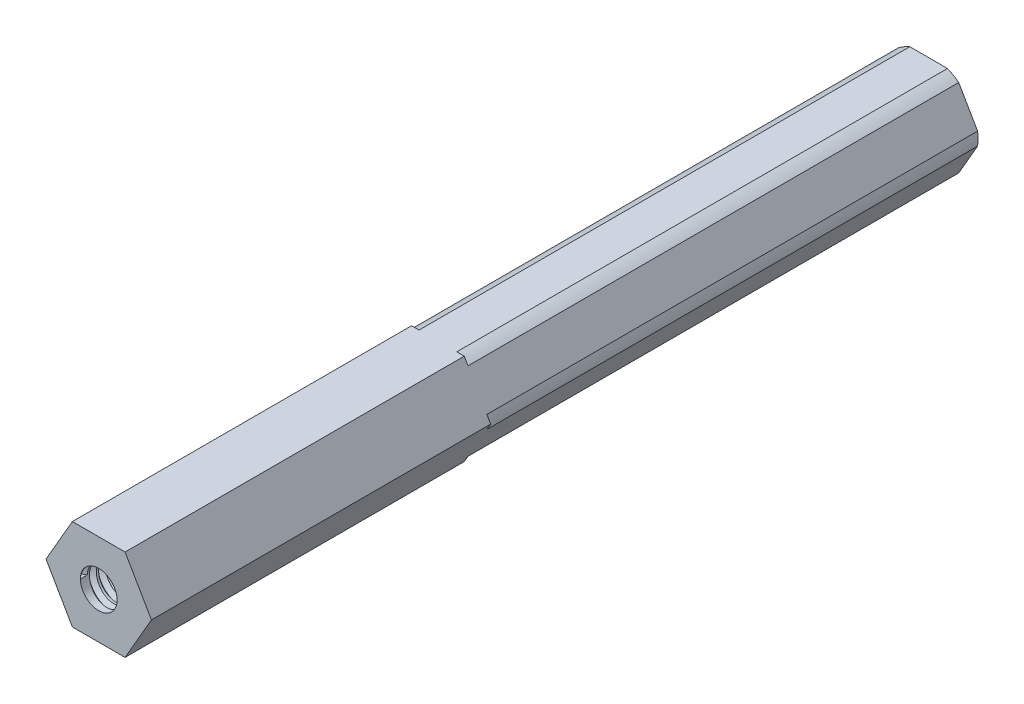
SolidWorks part; units mm, degrees
material "7075-T6 (SN)"
ref_plane "Alzado" through (0, 0, 0) normal (0, 0, 1) x (1, 0, 0)
ref_plane "Planta" through (0, 0, 0) normal (0, 1, 0) x (1, 0, 0)
ref_plane "Vista lateral" through (0, 0, 0) normal (1, 0, 0) x (0, 0, -1)
sketch "Croquis2" plane through (0, 0, 0) normal (0, 0, 1) x (1, 0, 0)
  line L1 (3.6662, -6.35) -> (7.3323, 0)
  line L2 (7.3323, 0) -> (3.6662, 6.35)
  line L3 (3.6662, 6.35) -> (-3.6662, 6.35)
  line L4 (-3.6662, 6.35) -> (-7.3323, 0)
  line L5 (-7.3323, 0) -> (-3.6662, -6.35)
  line L6 (-3.6662, -6.35) -> (3.6662, -6.35)
  circle A0 centre (0, 0) radius 6.35 construction
  dimension "D1" = 12.7
extrude "Extrusión Hex Profile" add sketch "Croquis2" along normal mid plane 115.4176
sketch "Croquis3" plane through (0, 0, 0) normal (0, 0, 1) x (1, 0, 0)
  circle A0 centre (0, 0) radius 2.5527
  dimension "D1" = 5.1054
extrude "Tap Hole 1" cut sketch "Croquis3" against normal blind 19.05 from surface starting at face at (0, 0, 57.7088)
extrude "Tap Hole 2" cut sketch "Croquis3<3>" along normal blind 19.05 from surface starting at face at (0, 0, -57.7088)
sketch "Croquis3<3>" plane through (0, 0, 0) normal (0, 0, 1) x (1, 0, 0) same geometry as "Croquis3"
sketch "Croquis7" plane through (0, 0, 0) normal (0, 0, 1) x (1, 0, 0)
  circle A0 centre (0, 0) radius 6.8707
  dimension "D1" = 13.7414
extrude "ThunderHex" cut sketch "Croquis7" along normal offset from surface (68.2498 mm away) 47.1678 from surface flip side to cut up to face at (2.5527, 0, 57.7088) starting at face at (2.5527, 0, -57.7088)
sketch "Croquis8" plane through (0, 0, 0) normal (0, 1, 0) x (1, 0, 0)
  line L0 (0, -57.7088) -> (-5.5562, -57.7088) construction
  line L1 (3.6662, -57.7088) -> (-3.6662, -57.7088) construction
  line L3 (0, -57.7088) -> (0, 0) construction
  line L4 (-5.5562, -57.7088) -> (-6.35, -56.915)
  line L5 (-6.35, -56.915) -> (-6.35, -56.1213)
  line L6 (-6.35, -56.1213) -> (-5.9055, -56.1213)
  line L7 (-5.9055, -56.1213) -> (-5.9055, -54.5338)
  line L8 (-5.9055, -54.5338) -> (-12.7, -54.5338)
  line L9 (-12.7, -54.5338) -> (-12.7, -57.7088)
  line L10 (-12.7, -57.7088) -> (-5.5562, -57.7088)
  line L11 (-3.6662, -57.7088) -> (-7.3323, -57.7088) construction
  dimension "D1" = 11.811
  dimension "D2" = 12.7
  dimension "D3" = 45
  dimension "D4" = 0.7937
  dimension "D6" = 0.7937
  dimension "D7" = 3.175
  dimension "D8" = 25.4
revolve "Retaining Ring 1" [suppressed] cut sketch "Croquis8" angle 360 about L3
sketch "Croquis9" plane through (0, 0, 0) normal (0, -1, 0) x (1, 0, 0)
  line L0 (0, -57.7088) -> (-5.5562, -57.7088) construction
  line L3 (0, -57.7088) -> (0, 0) construction
  line L4 (-5.5562, -57.7088) -> (-6.35, -56.915)
  line L5 (-6.35, -56.915) -> (-6.35, -56.1213)
  line L6 (-6.35, -56.1213) -> (-5.9055, -56.1213)
  line L7 (-5.9055, -56.1213) -> (-5.9055, -54.5338)
  line L8 (-5.9055, -54.5338) -> (-12.7, -54.5338)
  line L9 (-12.7, -54.5338) -> (-12.7, -57.7088)
  line L10 (-12.7, -57.7088) -> (-5.5562, -57.7088)
  line L12 (-2.6237, -57.7088) -> (2.6237, -57.7088) construction
  line L13 (-6.8111, -57.7088) -> (-4.1874, -57.7088) construction
  dimension "D1" = 11.811
  dimension "D2" = 12.7
  dimension "D3" = 45
  dimension "D4" = 0.7937
  dimension "D6" = 0.7937
  dimension "D7" = 3.175
  dimension "D8" = 25.4
revolve "Retaining Ring 2" [suppressed] cut sketch "Croquis9" angle 360 about L3
sketch "Croquis10" plane through (0, 0, 0) normal (0, 1, 0) x (1, 0, 0)
  line L0 (0, -57.7088) -> (0, 0) construction
  line L1 (3.6662, -57.7088) -> (-3.6662, -57.7088) construction
  line L2 (0, -57.7088) -> (-5.5562, -57.7088) construction
  line L3 (-3.6662, -57.7088) -> (-7.3323, -57.7088) construction
  line L4 (-5.5562, -57.7088) -> (-6.35, -56.915)
  line L5 (-6.35, -56.915) -> (-6.35, -49.7586)
  line L6 (-6.35, -49.7586) -> (-9.525, -49.7586)
  line L7 (-9.525, -49.7586) -> (-9.525, -57.7088)
  line L8 (-9.525, -57.7088) -> (-5.5562, -57.7088)
  dimension "D2" = 12.7
  dimension "D1" = 45
  dimension "D3" = 0.7937
  dimension "D4" = 7.9502
  dimension "D5" = 19.05
revolve "Round End 1" [suppressed] cut sketch "Croquis10" angle 360 about L0
sketch "Croquis12" plane through (0, 0, 0) normal (0, -1, 0) x (1, 0, 0)
  line L0 (0, -57.7088) -> (0, 0) construction
  line L2 (0, -57.7088) -> (-5.5562, -57.7088) construction
  line L4 (-5.5562, -57.7088) -> (-6.35, -56.915)
  line L5 (-6.35, -56.915) -> (-6.35, -49.7586)
  line L6 (-6.35, -49.7586) -> (-9.525, -49.7586)
  line L7 (-9.525, -49.7586) -> (-9.525, -57.7088)
  line L8 (-9.525, -57.7088) -> (-5.5562, -57.7088)
  line L9 (-2.6237, -57.7088) -> (2.6237, -57.7088) construction
  dimension "D1" = 45
  dimension "D3" = 0.7937
  dimension "D4" = 7.9502
  dimension "D2" = 12.7
  dimension "D5" = 19.05
revolve "Round End 2" [suppressed] cut sketch "Croquis12" angle 360 about L0
thread "Rosca1" pitch 1.27 method cut profile "Perfil de rosca1" start angle 0, offset 0, length 0, pitch 1.27, diameter 5.1054
ref_plane "Plano1" through (-2.5527, 0, 57.7088) normal (0, -1, 0) x (-1, 0, 0)
sketch "Perfil de rosca1" plane through (-2.5527, 0, 57.7088) normal (0, -1, 0) x (-1, 0, 0)
  line L0 (0, 0) -> (0, 1.27) construction
  line L1 (0, 0) -> (0.6874, 0.3969)
  line L2 (0.6874, 0.3969) -> (0.6874, 0.5556)
  line L3 (0.6874, 0.5556) -> (0, 0.9525)
  line L4 (0.6874, 0.4762) -> (0, 0.4762) construction
  line L11 (0, 0) -> (0, 0.9525)
  point P2 (0, 0)
  dimension "Pitch" = 1.27
  dimension "Profile_Angle" = 60
  dimension "Profile_Land" = 0.1588
  dimension "Profile_Height" = 0.6874
thread "Rosca2" pitch 1.27 method cut profile "Perfil de rosca2" start angle 0, offset 0, length 0, pitch 1.27, diameter 5.1054
ref_plane "Plano2" through (2.5527, 0, -57.7088) normal (0, -1, 0) x (1, 0, 0)
sketch "Perfil de rosca2" plane through (2.5527, 0, -57.7088) normal (0, -1, 0) x (1, 0, 0)
  line L0 (0, 0) -> (0, 1.27) construction
  line L1 (0, 0) -> (0.6874, 0.3969)
  line L2 (0.6874, 0.3969) -> (0.6874, 0.5556)
  line L3 (0.6874, 0.5556) -> (0, 0.9525)
  line L4 (0.6874, 0.4762) -> (0, 0.4762) construction
  line L11 (0, 0) -> (0, 0.9525)
  point P2 (0, 0)
  dimension "Pitch" = 1.27
  dimension "Profile_Angle" = 60
  dimension "Profile_Land" = 0.1588
  dimension "Profile_Height" = 0.6874
equation "\"HexOD\"= 0.5pulgadas"
equation "\"Largo\"= 4.544pulgadas"
equation "\"D1@Croquis2\"=\"HexOD\""
equation "\"D1@Extrusión Hex Profile\" = \"Largo\""
equation "\"TapHole\"= IIF ( \"HexOD\" = 0.5pulgadas , 0.2010pulgadas , 0.190pulgadas )"
equation "\"D1@Croquis3\"=\"TapHole\""
equation "\"ProTapHole\"= 0.75pulgadas"
equation "\"D1@Tap Hole 1\" = \"ProTapHole\""
equation "\"D1@Tap Hole 2\" = \"ProTapHole\""
equation "\"ThunderHex\"= IIF ( \"HexOD\" = 0.5pulgadas , 0.541pulgadas , 0.4035pulgadas )"
equation "\"D1@Croquis7\"=\"ThunderHex\""
equation "\"D2@Croquis8\"=\"HexOD\""
equation "\"D1@Croquis8\"=if(\"HexOD\"=0.5pulgadas, 0.465pulgadas, 0.35pulgadas )"
equation "\"D2@Croquis9\"=\"HexOD\""
equation "\"D1@Croquis9\"=if(\"HexOD\"=0.5pulgadas, 0.465pulgadas, 0.35pulgadas )"
equation "\"D8@Croquis8\"=\"HexOD\"*2"
equation "\"D8@Croquis9\"=\"HexOD\"*2"
equation "\"D5@Croquis10\"=\"HexOD\"*1.5"
equation "\"D5@Croquis12\"=\"HexOD\"*1.5"
equation "\"D4@Croquis10\"=if( \"D2@Croquis10\"=<0.375, 0.28, 0.313)"
equation "\"D4@Croquis12\"=if( \"D2@Croquis10\"=<0.375, 0.28, 0.313)"
